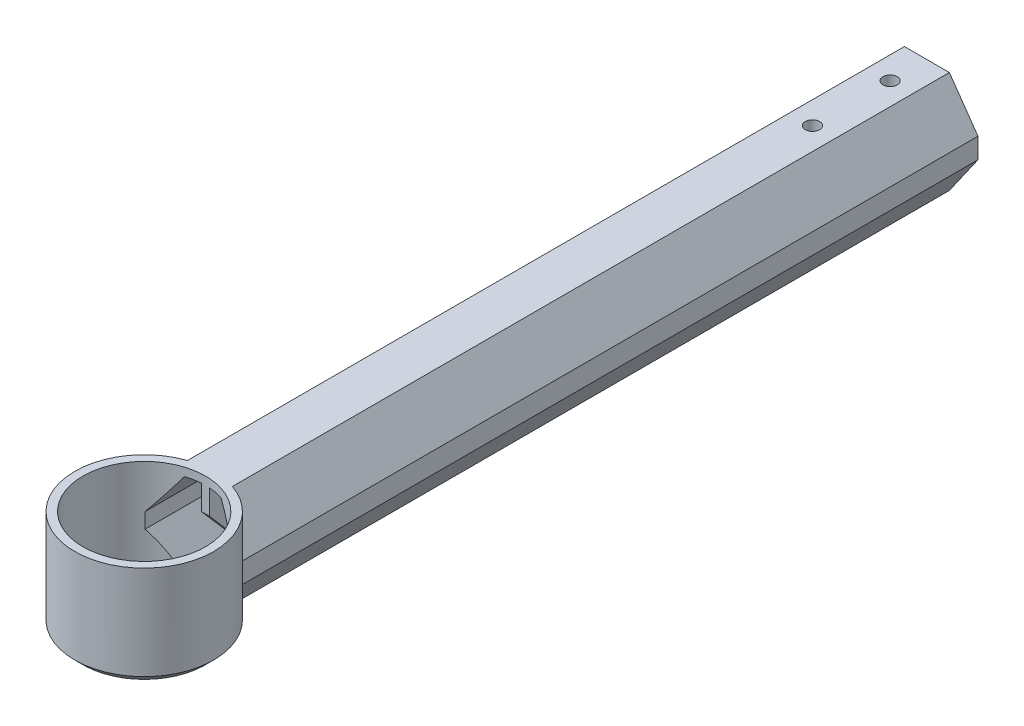
SolidWorks part; units mm, degrees
material "ABS generico"
ref_plane "Piano frontale" through (0, 0, 0) normal (0, 0, 1) x (1, 0, 0)
ref_plane "Piano superiore" through (0, 0, 0) normal (0, 1, 0) x (1, 0, 0)
ref_plane "Piano destro" through (0, 0, 0) normal (1, 0, 0) x (0, 0, -1)
sketch "Schizzo1" plane through (0, 0, 0) normal (0, 0, 1) x (1, 0, 0)
  line L0 (3.6233, 15.123) -> (10.6233, 5.123)
  line L1 (-7.3767, 15.123) -> (3.6233, 15.123)
  line L2 (-7.3767, 15.123) -> (-7.3767, -9.877) construction
  line L3 (-7.3767, -9.877) -> (3.6233, -9.877)
  line L4 (-7.3767, -9.877) -> (-7.3597, -9.8281)
  line L5 (-6.3354, 13.123) -> (-12.3767, 4.4925)
  line L6 (-14.3767, 5.123) -> (-14.3767, 0.123)
  line L7 (-6.3354, 13.123) -> (2.582, 13.123)
  line L8 (10.6233, 5.123) -> (10.6233, 0.123)
  line L9 (10.6233, 0.123) -> (3.6233, -9.877)
  line L10 (-7.3767, -9.877) -> (-14.3767, 0.123)
  line L11 (-14.3767, 5.123) -> (-7.3767, 15.123)
  line L12 (-14.3767, 0.123) -> (10.6233, 0.123) construction
  line L13 (-6.3354, -7.877) -> (2.582, -7.877)
  line L15 (-2.8767, 13.123) -> (-0.8767, 13.123)
  line L16 (-12.3767, 4.4925) -> (-12.3767, 0.7534)
  line L17 (-2.8767, 13.123) -> (-2.8767, -7.877)
  line L18 (8.6233, 4.4925) -> (8.6233, 0.7534)
  line L19 (-12.3767, 0.7534) -> (-6.3354, -7.877)
  line L20 (2.582, -7.877) -> (8.6233, 0.7534)
  line L21 (8.6233, 4.4925) -> (2.582, 13.123)
  line L22 (-2.8767, -7.877) -> (-0.8767, -7.877)
  line L23 (-0.8767, 13.123) -> (-0.8767, -7.877)
  dimension "D1" = 11
  dimension "D2" = 5
  dimension "D3" = 25
  dimension "D4" = 25
  dimension "D5" = 2
  dimension "D6" = 2
  dimension "D7" = 2
  dimension "D8" = 2
  dimension "D9" = 2
  dimension "D10" = 2
  dimension "D11" = 9.5
extrude "Estrusione-Estrusione1" add sketch "Schizzo1" along normal blind 180 contours L11 L6 L10 L3 L9 L8 L0 L1 L21 L18 L20 L13 L19 L16 L5 L7 | L23 L7 L17 L13 region at (6.8336, 9.9202, 0) region at (-1.8767, 2.623, 0)
sketch "Schizzo3" plane through (0, 15.123, 0) normal (0, 1, 0) x (1, 0, 0)
  circle A0 centre (-1.8767, -191.5217) radius 17
  dimension "D1" = 34
extrude "Taglio-Estrusione2" cut sketch "Schizzo3" against normal through all
sketch "Schizzo4" plane through (0, 15.123, 0) normal (0, 1, 0) x (1, 0, 0)
  circle A0 centre (-1.8767, -191.5217) radius 17 construction
  arc A1 (3.6233, -175.436) -> (-7.3767, -175.436) centre (-1.8767, -191.5217) ccw construction
  arc A2 (-7.3767, -175.436) -> (3.6233, -175.436) centre (-1.8767, -191.5217) ccw
  circle A3 centre (-1.8767, -191.5217) radius 15 construction
  circle A4 centre (-1.8767, -191.5217) radius 15
  arc M5 (-7.3767, -175.436) -> (3.6233, -175.436) centre (-1.8767, -191.5217) cw
  dimension "D1" = 34
  dimension "D2" = 30
extrude "Estrusione-Estrusione2" add sketch "Schizzo4" against normal through all contours A2 A4 M5 region at (-1.8767, 15.123, 175.0026)
sketch "Schizzo6" plane through (0, -9.877, 0) normal (0, -1, 0) x (1, 0, 0)
  circle A0 centre (-1.8767, 191.5217) radius 15
extrude "Estrusione-Estrusione3" add sketch "Schizzo6" against normal blind 2
sketch "Schizzo8" plane through (0, 0, 0) normal (0, 0, -1) x (-1, 0, 0)
  line L0 (0.8767, -7.877) -> (-2.582, -7.877)
  line L1 (-2.582, -7.877) -> (-8.6233, 0.7534)
  line L2 (-8.6233, 0.7534) -> (-8.6233, 4.4925)
  line L3 (-8.6233, 4.4925) -> (-2.582, 13.123)
  line L4 (-2.582, 13.123) -> (0.8767, 13.123)
  line L5 (0.8767, 13.123) -> (0.8767, -7.877)
  line L6 (2.8767, -7.877) -> (2.8767, 13.123)
  line L7 (2.8767, 13.123) -> (6.3354, 13.123)
  line L8 (6.3354, 13.123) -> (12.3767, 4.4925)
  line L9 (12.3767, 4.4925) -> (12.3767, 0.7534)
  line L10 (12.3767, 0.7534) -> (6.3354, -7.877)
  line L11 (6.3354, -7.877) -> (2.8767, -7.877)
extrude "Taglio-Estrusione4" cut sketch "Schizzo8" against normal up to next
sketch "Schizzo10" plane through (-0.8767, 0, 0) normal (1, 0, 0) x (0, 0, -1)
  line L0 (-176.5551, -7.877) -> (-176.5551, 7.123)
  line L1 (-176.5551, 7.123) -> (-163.5551, -7.877)
  line L2 (-176.5551, -7.877) -> (0, -7.877) construction
  line L3 (-163.5551, -7.877) -> (-176.5551, -7.877)
  line L4 (-176.5551, 13.123) -> (-176.5551, -7.877) construction
  dimension "D1" = 6
  dimension "D2" = 13
extrude "Taglio-Estrusione5" cut sketch "Schizzo10" against normal up to next
sketch "Schizzo11" plane through (0, -7.877, 0) normal (0, 1, 0) x (1, 0, 0)
  circle A0 centre (-1.8767, -191.5217) radius 15
extrude "Estrusione-Estrusione4" add sketch "Schizzo11" along normal blind 1
chamfer "Smusso1" distance 2 angle 30 1 edges at (-1.8767, -7.877, 176.5217) first distance on face at (-1.8767, -7.877, 85.104)
chamfer "Smusso2" distance 2 angle 45 1 edges at (-1.8767, -9.877, 208.5217)
sketch "Schizzo12" plane through (0, -6.877, 0) normal (0, 1, 0) x (1, 0, 0)
  circle A0 centre (-1.8767, -191.5217) radius 2.5
  dimension "D1" = 5
extrude "Taglio-Estrusione6" cut sketch "Schizzo12" against normal through all
sketch "Schizzo13" plane through (0, -6.877, 0) normal (0, 1, 0) x (1, 0, 0)
  circle A0 centre (-1.8767, -191.5217) radius 4.75
  circle A1 centre (-1.8767, -191.5217) radius 2.5 construction
  dimension "D1" = 9.5
extrude "Taglio-Estrusione7" cut sketch "Schizzo13" against normal blind 2
sketch "Schizzo14" plane through (0, -6.877, 0) normal (0, 1, 0) x (1, 0, 0)
  circle A0 centre (-7.5233, -197.1888) radius 1.2295 construction
  circle A1 centre (4.853, -198.227) radius 1.2295 construction
  circle A2 centre (3.7698, -185.8546) radius 1.2295 construction
  circle A3 centre (-8.6064, -184.8164) radius 1.2295 construction
  circle A7 centre (4.853, -198.227) radius 1.5
  circle A16 centre (-8.6064, -184.8164) radius 1.5
  circle A17 centre (-8.6064, -184.8164) radius 1.5
  circle A18 centre (-7.5233, -197.1888) radius 1.5
  circle A19 centre (3.7698, -185.8546) radius 1.5
  point P56 (-15.9445, -181.5343)
  point P73 (-1.8767, -191.5217)
  point P106 (-15.9445, -181.5343)
  dimension "D3" = 2
  dimension "D5" = 3
extrude "Taglio-Estrusione9" cut sketch "Schizzo14" against normal through all contours A16 | A19 | A7 | A18
sketch "Schizzo15" plane through (0, 15.123, 0) normal (0, 1, 0) x (1, 0, 0)
  line L0 (-1.8767, 0) -> (-1.8767, -52.0289) construction
  line L1 (-7.3767, 0) -> (3.6233, 0) construction
  circle A0 centre (-1.8767, -28) radius 3.75
  circle A1 centre (-1.8767, -9) radius 3.75
  dimension "D1" = 7.5
  dimension "D2" = 9
  dimension "D3" = 19
extrude "Estrusione-Estrusione5" add sketch "Schizzo15" against normal blind 25
sketch "Schizzo16" plane through (0, 15.123, 0) normal (0, 1, 0) x (1, 0, 0)
  circle A0 centre (-1.8767, -28) radius 1.75
  circle A1 centre (-1.8767, -9) radius 1.75
  arc A2 (-2.8767, -24.3858) -> (-2.8767, -31.6142) centre (-1.8767, -28) ccw construction
  dimension "D1" = 3.5
extrude "Taglio-Estrusione10" cut sketch "Schizzo16" against normal through all
sketch "Schizzo17" plane through (0, -6.877, 0) normal (0, 1, 0) x (1, 0, 0)
  line L0 (-7.5233, -197.1888) -> (3.7698, -185.8546) construction
  line L1 (4.853, -198.227) -> (-8.6064, -184.8164) construction
  line L2 (4.853, -198.227) -> (8.0408, -201.4032) construction
  line L3 (-7.5233, -197.1888) -> (-11.7582, -201.4392) construction
  line L4 (3.7698, -185.8546) -> (8.0048, -181.6042) construction
  line L5 (-8.6064, -184.8164) -> (-11.7942, -181.6402) construction
  line L6 (3.7698, -185.8546) -> (3.7904, -197.1683) construction
  line L7 (3.7904, -197.1683) -> (-7.5233, -197.1888) construction
  line L8 (-7.5233, -197.1888) -> (-7.5233, -185.8956) construction
  line L9 (-7.5233, -185.8956) -> (3.7698, -185.8546) construction
  line L10 (12.1233, -191.5217) -> (-15.8767, -191.5217) construction
  line L11 (-1.8767, -205.5217) -> (-1.8767, -177.5217) construction
  line L12 (-8.7854, -193.0027) -> (-8.7854, -190.0407) construction
  line L13 (-8.7854, -190.0407) -> (-13.6502, -189.2592)
  line L14 (-8.7854, -193.0027) -> (-13.6502, -193.7843)
  line L15 (-13.6502, -189.2592) -> (-13.6502, -193.7843) construction
  line L16 (-0.3957, -184.6131) -> (0.3858, -179.7482)
  line L17 (-3.3577, -184.6131) -> (-4.1393, -179.7482)
  line L18 (-3.3577, -184.6131) -> (-0.3957, -184.6131) construction
  line L19 (0.3858, -179.7482) -> (-4.1393, -179.7482) construction
  line L20 (5.0319, -193.0027) -> (9.8968, -193.7843)
  line L21 (5.0319, -190.0407) -> (9.8968, -189.2592)
  line L22 (5.0319, -190.0407) -> (5.0319, -193.0027) construction
  line L23 (9.8968, -193.7843) -> (9.8968, -189.2592) construction
  line L24 (-3.3577, -198.4304) -> (-4.1393, -203.2952)
  line L25 (-0.3957, -198.4304) -> (0.3858, -203.2952)
  line L26 (-0.3957, -198.4304) -> (-3.3577, -198.4304) construction
  line L27 (-4.1393, -203.2952) -> (0.3858, -203.2952) construction
  circle A0 centre (-1.8767, -191.5217) radius 6.5 construction
  circle A1 centre (3.7698, -185.8546) radius 1.5 construction
  circle A2 centre (-1.8767, -191.5217) radius 14 construction
  arc A3 (-7.0354, -177.4367) -> (3.282, -177.4367) centre (-1.8767, -191.5217) ccw construction
  circle A4 centre (4.853, -198.227) radius 1.5 construction
  arc A5 (-8.7854, -190.0407) -> (-8.7854, -193.0027) centre (-9.0233, -191.5217) cw
  arc A6 (-13.6502, -193.7843) -> (-13.6502, -189.2592) centre (-13.6139, -191.5217) cw
  arc A7 (-0.3957, -184.6131) -> (-3.3577, -184.6131) centre (-1.8767, -184.3752) cw
  arc A8 (-4.1393, -179.7482) -> (0.3858, -179.7482) centre (-1.8767, -179.7846) cw
  arc A9 (5.0319, -193.0027) -> (5.0319, -190.0407) centre (5.2698, -191.5217) cw
  arc A10 (9.8968, -189.2592) -> (9.8968, -193.7843) centre (9.8604, -191.5217) cw
  arc A11 (-3.3577, -198.4304) -> (-0.3957, -198.4304) centre (-1.8767, -198.6683) cw
  arc A12 (0.3858, -203.2952) -> (-4.1393, -203.2952) centre (-1.8767, -203.2589) cw
  point P56 (-1.8767, -191.5217)
  dimension "D1" = 1
  dimension "D2" = 1.5
  dimension "D3" = 1.5
  dimension "D4" = 4
extrude "Taglio-Estrusione11" cut sketch "Schizzo17" against normal through all
